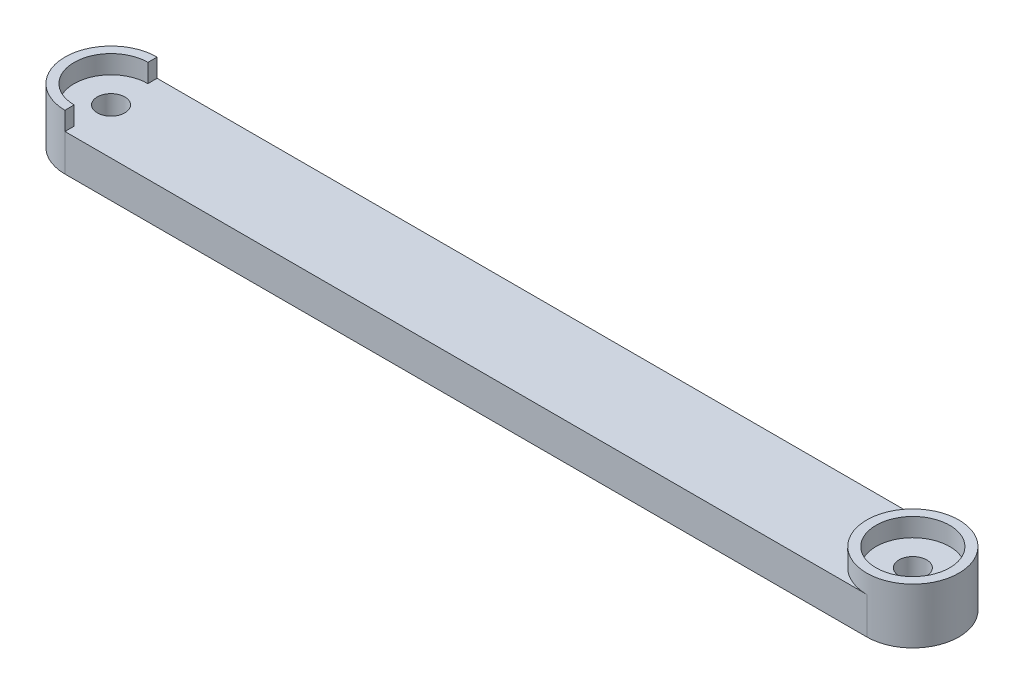
SolidWorks part; units mm, degrees
ref_plane "Front Plane" through (0, 0, 0) normal (0, 0, 1) x (1, 0, 0)
ref_plane "Top Plane" through (0, 0, 0) normal (0, 1, 0) x (1, 0, 0)
ref_plane "Right Plane" through (0, 0, 0) normal (1, 0, 0) x (0, 0, -1)
sketch "Sketch2" plane through (0, 0, 0) normal (0, 1, 0) x (1, 0, 0)
  line L0 (-21.75, 0) -> (21.75, 0) construction
  line L1 (-21.75, 2.5) -> (21.75, 2.5)
  line L2 (-21.75, -2.5) -> (21.75, -2.5)
  arc A0 (-21.75, 2.5) -> (-21.75, -2.5) centre (-21.75, 0) ccw
  arc A1 (21.75, -2.5) -> (21.75, 2.5) centre (21.75, 0) ccw
  circle A2 centre (-21.75, 0) radius 0.75
  circle A3 centre (21.75, 0) radius 0.75
  point P3 (0, 0)
  dimension "D2" = 2.5
  dimension "D3" = 1.5
  dimension "D1" = 43.5
extrude "Boss-Extrude1" add sketch "Sketch2" along normal blind 2
sketch "Sketch3" plane through (0, 2, 0) normal (0, 1, 0) x (1, 0, 0)
  line L0 (-21.75, 2.5) -> (-21.75, 2)
  line L1 (-21.75, -2) -> (-21.75, -2.5)
  arc A0 (-21.75, 2.5) -> (-21.75, -2.5) centre (-21.75, 0) ccw
  circle A1 centre (21.75, 0) radius 2.5
  circle A2 centre (21.75, 0) radius 2
  arc A3 (-21.75, 2) -> (-21.75, -2) centre (-21.75, 0) ccw
  arc A4 (-21.75, 2.5) -> (-21.75, -2.5) centre (-21.75, 0) ccw construction
  dimension "D1" = 4
extrude "Boss-Extrude2" add sketch "Sketch3" along normal blind 1
